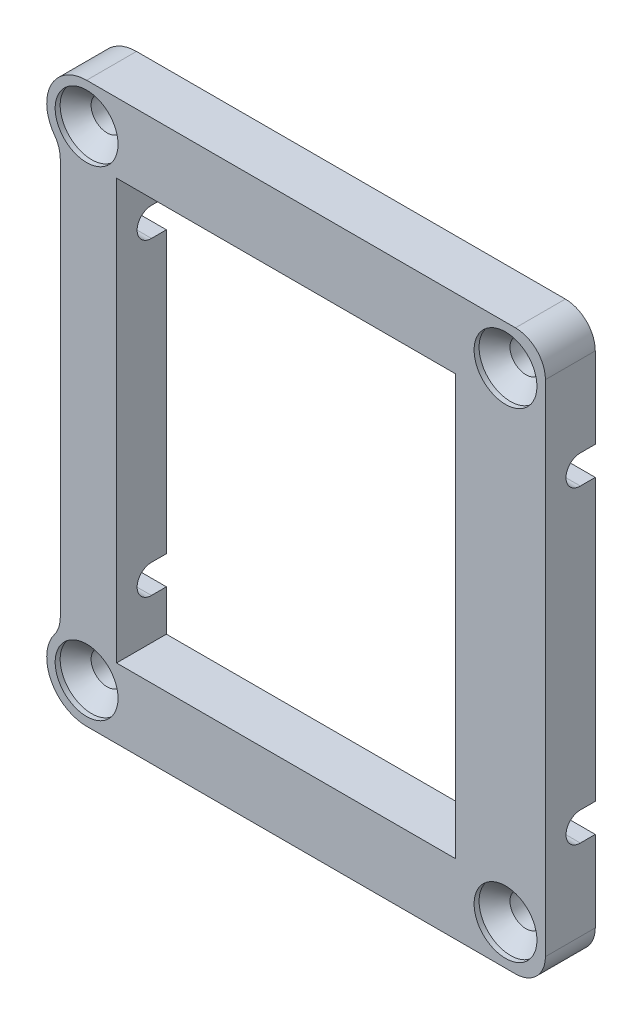
SolidWorks part; units mm, degrees
material "ABS"
ref_plane "Front Plane" through (0, 0, 0) normal (0, 0, 1) x (1, 0, 0)
ref_plane "Top Plane" through (0, 0, 0) normal (0, 1, 0) x (1, 0, 0)
ref_plane "Right Plane" through (0, 0, 0) normal (1, 0, 0) x (0, 0, -1)
sketch "Sketch1" plane through (0, 0, 0) normal (0, 0, 1) x (1, 0, 0)
  line L0 (23.0539, -73.6389) -> (23.0539, -115.7389)
  line L1 (20.0539, -66.6389) -> (63.0539, -66.6389)
  line L2 (17.4139, -73.644) -> (17.4139, -115.7339)
  line L3 (20.0539, -122.7389) -> (63.0539, -122.7389)
  line L4 (66.0539, -69.6389) -> (66.0539, -119.7389)
  line L10 (23.0539, -115.7389) -> (59.0539, -115.7389)
  line L12 (59.0539, -73.6389) -> (59.0539, -115.7389)
  line L13 (59.0539, -73.6389) -> (23.0539, -73.6389)
  line L15 (66.0539, -101.9889) -> (66.0539, -117.3889) construction
  line L17 (17.4139, -89.1889) -> (17.4139, -76.6389) construction
  arc A0 (63.0539, -66.6389) -> (66.0539, -69.6389) centre (63.0539, -69.6389) cw
  arc A3 (63.0539, -122.7389) -> (66.0539, -119.7389) centre (63.0539, -119.7389) ccw
  circle A4 centre (20.0539, -70.6389) radius 1.25
  circle A5 centre (20.0539, -118.7389) radius 1.25
  circle A6 centre (62.0539, -70.6389) radius 1.25
  circle A7 centre (62.0539, -118.7389) radius 1.25
  arc A8 (20.0539, -66.6389) -> (17.4139, -73.644) centre (20.0539, -70.6389) ccw
  arc A9 (17.4139, -115.7339) -> (20.0539, -122.7389) centre (20.0539, -118.7389) ccw
  dimension "D3" = 3
  dimension "D1" = 7
  dimension "D2" = 7
extrude "Boss-Extrude1" add sketch "Sketch1" along normal blind 5
sketch "Sketch6" plane through (0, 0, 5) normal (0, 0, 1) x (1, 0, 0)
  line L0 (59.0539, -73.6389) -> (23.0539, -73.6389) construction
  line L1 (59.0539, -115.7389) -> (57.0539, -115.7389)
  line L2 (59.0539, -115.7389) -> (59.0539, -73.6389)
  line L3 (59.0539, -73.6389) -> (57.0539, -73.6389)
  line L4 (57.0539, -115.7389) -> (57.0539, -73.6389)
extrude "Boss-Extrude4" add sketch "Sketch6" against normal up to vertex (5 mm away) up to point (59.0539, -115.7389, 0)
hole_wizard "CSK for M3 Countersunk Flat Head Screw1" positions "Sketch3" profile "Sketch2" countersink size "M3" standard "ISO" end condition through all
sketch "Sketch3" plane through (0, 0, 5) normal (0, 0, 1) x (1, 0, 0)
  point P0 (20.0539, -118.7389)
  point P2 (20.0539, -70.6389)
  point P4 (62.0539, -70.6389)
  point P6 (62.0539, -118.7389)
sketch "Sketch2" plane through (20.0539, -118.7389, 5) normal (1, 0, 0) x (0, -1, 0)
  line L0 (0, 0) -> (0, 5)
  line L1 (0, 5) -> (1.6, 5)
  line L2 (1.6, 5) -> (1.6, 2.05)
  line L3 (1.6, 2.05) -> (3.15, 0.5)
  line L4 (3.15, 0.5) -> (3.15, 0)
  line L6 (3.15, 0) -> (0, 0)
  line L7 (-1.6, 2.05) -> (-3.15, 0.5) construction
  line L11 (0, -6.35) -> (0, 107.95) construction
  dimension "Thru Hole Dia." = 3.2
  dimension "Thru Hole Depth" = 5
  dimension "C'Sink Dia." = 6.3
  dimension "C'Sink Angle" = 90
  dimension "Head Clearance" = 0.5
hole_wizard "Furo com folga de M34" positions "Sketch5" profile "Sketch4" hole size "M3" standard "Ansi Metric" end condition through all
sketch "Sketch5" plane through (66.0539, 0, 0) normal (1, 0, 0) x (0, 0, -1)
  circle A1 centre (-1.5, -110.1889) radius 1.5
  circle A3 centre (-1.5, -79.1889) radius 1.5
  point P0 (-1.5, -79.1889)
  point P2 (-1.5, -110.1889)
sketch "Sketch4" plane through (66.0539, -79.1889, 1.5) normal (0, 1, 0) x (0, 0, -1)
  line L0 (0, 0) -> (0, 50)
  line L1 (0, 50) -> (1.435, 50)
  line L2 (1.435, 50) -> (1.435, 0)
  line L5 (1.435, 0) -> (0, 0)
  line L11 (0, -6.35) -> (0, 107.95) construction
  dimension "Thru Hole Dia." = 2.87
  dimension "Thru Hole Depth" = 50
fillet "Filete1" radius 3 2 edges at (17.4139, -115.7339, 2.5) (17.4139, -73.644, 2.5)
sketch "Esboço3" plane through (57.0539, 0, 0) normal (-1, 0, 0) x (0, 0, 1)
  line L1 (1.5, -80.6239) -> (0, -80.6239)
  line L2 (1.5, -80.6239) -> (1.5, -77.7539)
  line L3 (1.5, -77.7539) -> (0, -77.7539)
  line L4 (0, -80.6239) -> (0, -77.7539)
  line L5 (0, -73.6389) -> (0, -115.7389) construction
  line L6 (1.5, -108.7539) -> (0, -108.7539)
  line L7 (1.5, -108.7539) -> (1.5, -111.6239)
  line L8 (1.5, -111.6239) -> (0, -111.6239)
  line L9 (0, -108.7539) -> (0, -111.6239)
  circle A0 centre (1.5, -79.1889) radius 1.435 construction
  circle A1 centre (1.5, -110.1889) radius 1.435 construction
  circle A4 centre (1.5, -110.1889) radius 1.435 construction
extrude "Corte-extrusão1" cut sketch "Esboço3" along normal blind 63 and the other way blind 10
